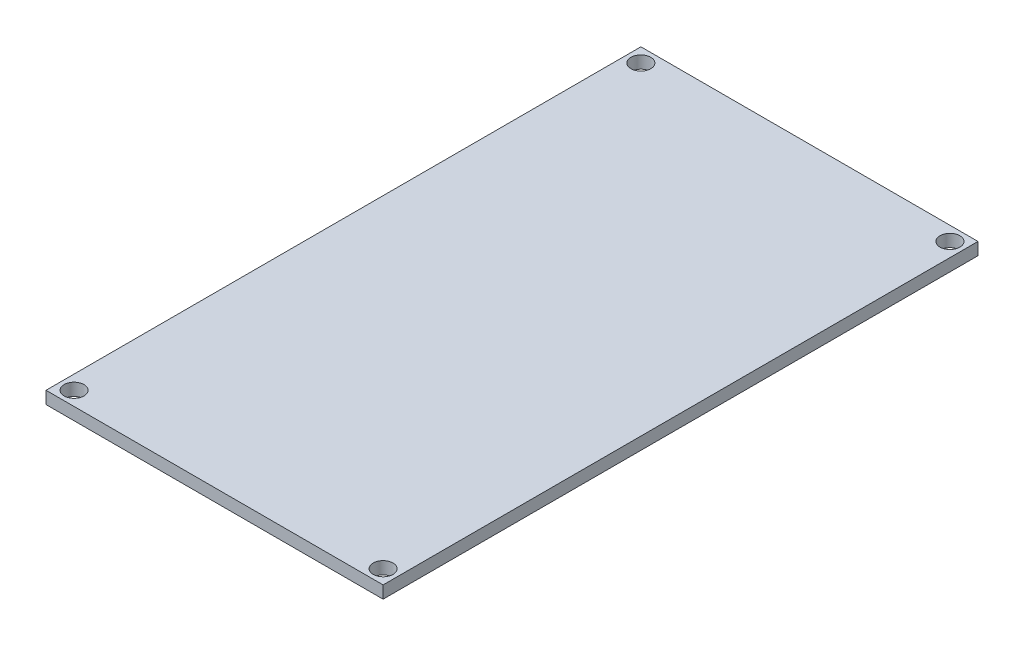
SolidWorks part; units mm, degrees
material "Glass"
ref_plane "Front Plane" through (0, 0, 0) normal (0, 0, 1) x (1, 0, 0)
ref_plane "Top Plane" through (0, 0, 0) normal (0, 1, 0) x (1, 0, 0)
ref_plane "Right Plane" through (0, 0, 0) normal (1, 0, 0) x (0, 0, -1)
sketch "Sketch3" plane through (0, 0, 0) normal (0, 1, 0) x (1, 0, 0)
  line L1 (-17, 26) -> (-17, 35.8093)
  line L2 (-17, 35.8093) -> (-7.1907, 35.8093)
  line L4 (0, 22.5721) -> (0, 0) construction
  line L6 (-17, 5.8093) -> (17, 5.8093) construction
  line L8 (17, 26) -> (17, -14.3815)
  line L9 (-17, 35.8093) -> (-14.1716, 32.9808) construction
  line L11 (-17, 35.8093) -> (-17, 26)
  line L12 (-7.1907, 35.8093) -> (-17, 35.8093)
  line L13 (17, 35.8093) -> (14.1716, 32.9808) construction
  line L14 (7.1907, 35.8093) -> (17, 35.8093)
  line L15 (17, 35.8093) -> (17, 26)
  line L16 (17, 35.8093) -> (7.1907, 35.8093)
  line L17 (17, 26) -> (17, 35.8093)
  line L18 (17, -24.1907) -> (14.1716, -21.3623) construction
  line L19 (-17, -24.1907) -> (-14.1716, -21.3623) construction
  line L20 (17, -14.3815) -> (17, -24.1907)
  line L21 (17, -24.1907) -> (7.1907, -24.1907)
  line L22 (17, -24.1907) -> (17, -14.3815)
  line L23 (7.1907, -24.1907) -> (17, -24.1907)
  line L24 (-7.1907, -24.1907) -> (-17, -24.1907)
  line L25 (-17, -24.1907) -> (-17, -14.3815)
  line L26 (-17, -24.1907) -> (-7.1907, -24.1907)
  line L27 (-17, -14.3815) -> (-17, -24.1907)
  line L31 (7.1907, -24.1907) -> (-7.1907, -24.1907)
  line L32 (-17, -14.3815) -> (-17, 26)
  line L33 (-7.1907, 35.8093) -> (7.1907, 35.8093)
  circle A1 centre (-15.5858, 34.3951) radius 1
  circle A6 centre (15.5858, 34.3951) radius 1
  circle A7 centre (15.5858, -22.7765) radius 1
  circle A10 centre (-15.5858, -22.7765) radius 1
  point P2 (0, 0)
  point P3 (-17, 5.8093)
  point P4 (0, 0)
  point P5 (-13.7774, 26.8069)
  point P10 (0, 0)
  point P11 (0, 30)
  point P13 (0, 22.5721)
  dimension "D2" = 2
  dimension "D1" = 1.4142
  dimension "D3" = 30
  dimension "D4" = 17
  dimension "D5" = 35.8093
extrude "Boss-Extrude1" add sketch "Sketch3" along normal blind 1.25 contours L33 L2 L1 L32 L25 L24 L31 L21 L20 L8 L15 L14 A6 A1 A7 A10 region at (0, 0, -5.8093)
